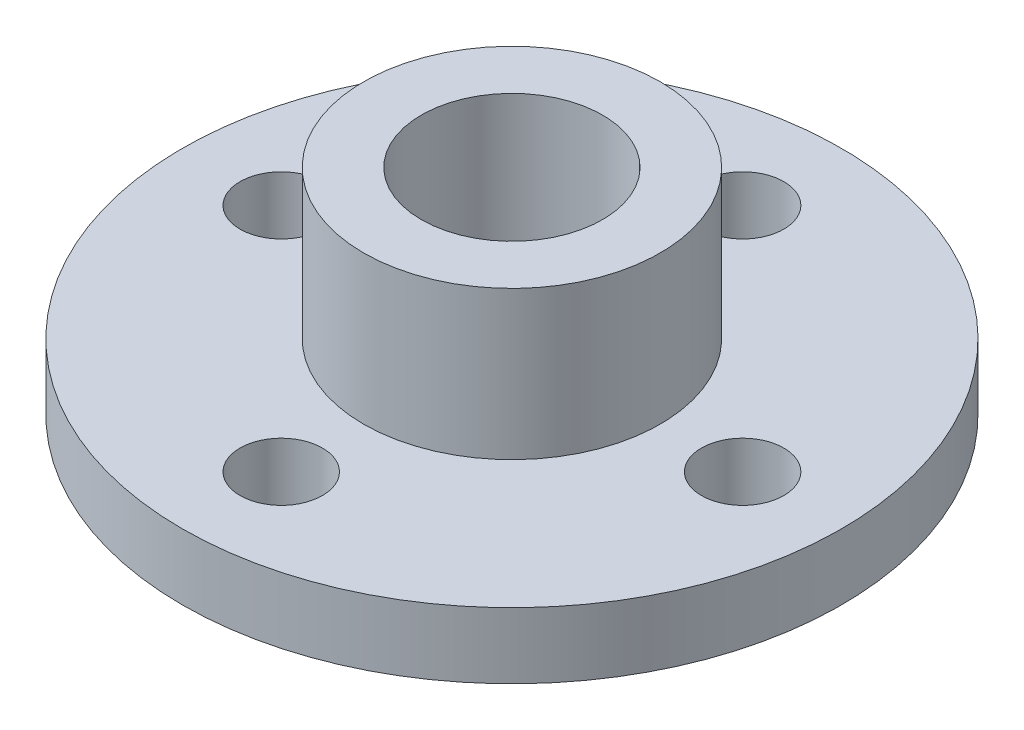
SolidWorks part; units mm, degrees
ref_plane "Front Plane" through (0, 0, 0) normal (0, 0, 1) x (1, 0, 0)
ref_plane "Top Plane" through (0, 0, 0) normal (0, 1, 0) x (1, 0, 0)
ref_plane "Right Plane" through (0, 0, 0) normal (1, 0, 0) x (0, 0, -1)
sketch "Sketch2" plane through (0, 0, 0) normal (0, 1, 0) x (1, 0, 0)
  circle A0 centre (0, 0) radius 10
  circle A1 centre (0, 0) radius 4.5
  circle A2 centre (0, 0) radius 2.75
  dimension "D1" = 20
  dimension "D2" = 9
  dimension "D3" = 5.5
extrude "Boss-Extrude1" add sketch "Sketch2" against normal blind 2 contours A0
extrude "Boss-Extrude2" add sketch "Sketch2<3>" along normal blind 4.5 contours A1 A2 region at (-4.3727, 0, 0)
sketch "Sketch2<3>" plane through (0, 0, 0) normal (0, 1, 0) x (1, 0, 0) same geometry as "Sketch2"
sketch "Sketch4" plane through (0, 0, 0) normal (0, 1, 0) x (1, 0, 0)
  circle A0 centre (0, 0) radius 7
  point P3 (0, 7)
  dimension "D1" = 14
hole_wizard "Tap Drill for M3x0.5 Tap1" positions "Sketch4" profile "Sketch5" hole size "M3x0.5" standard "ANSI Metric"
sketch "Sketch5" plane through (0, 0, -7) normal (1, 0, 0) x (0, 0, 1)
  line L0 (0, 0) -> (0, 10.9111)
  line L1 (0, 10.9111) -> (1.25, 10.16)
  line L2 (1.25, 10.16) -> (1.25, 0)
  line L5 (1.25, 0) -> (0, 0)
  line L10 (0, 10.9111) -> (-1.25, 10.16) construction
  line L11 (0, -6.35) -> (0, 107.95) construction
  dimension "Hole Dia." = 2.5
  dimension "Hole Depth" = 10.16
  dimension "Drill Angle" = 118
pattern_circular "CirPattern1" count 4 over 360 about axis through (0, -2, 0) along (0, 1, 0) of "Tap Drill for M3x0.5 Tap1" reverse direction yes
